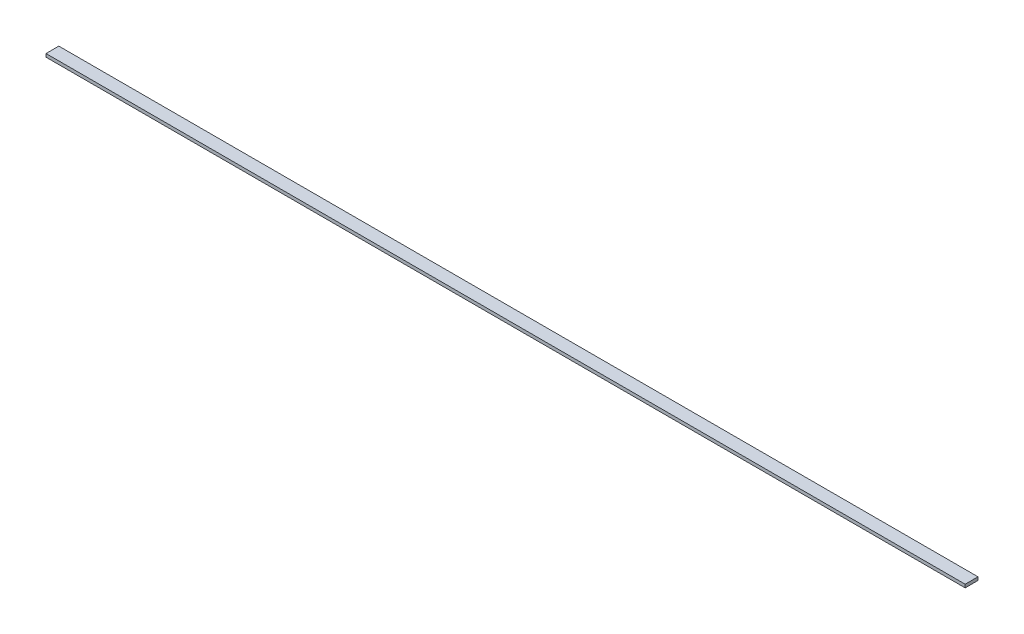
SolidWorks part; units mm, degrees
ref_plane "Front Plane" through (0, 0, 0) normal (0, 0, 1) x (1, 0, 0)
ref_plane "Top Plane" through (0, 0, 0) normal (0, 1, 0) x (1, 0, 0)
ref_plane "Right Plane" through (0, 0, 0) normal (1, 0, 0) x (0, 0, -1)
sketch "Sketch1" plane through (0, 0, 0) normal (0, 1, 0) x (1, 0, 0)
  line L1 (-215, 3) -> (215, 3)
  line L2 (-215, 3) -> (-215, -3)
  line L3 (-215, -3) -> (215, -3)
  line L4 (215, 3) -> (215, -3)
  line L5 (-215, 3) -> (215, -3) construction
  line L6 (-215, -3) -> (215, 3) construction
  point P0 (0, 0)
  dimension "D1" = 6
  dimension "D2" = 430
extrude "Boss-Extrude1" add sketch "Sketch1" along normal blind 1.5
